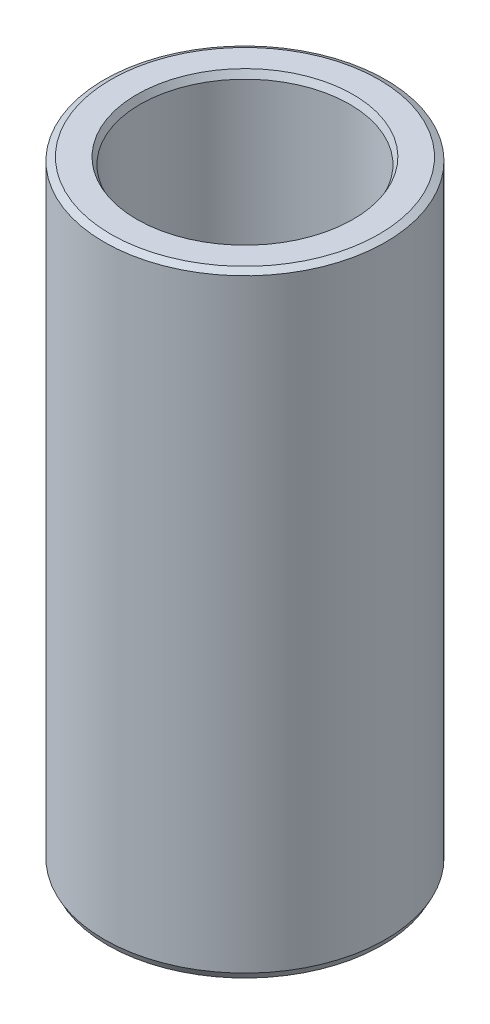
SolidWorks part; units mm, degrees
ref_plane "Front Plane" through (0, 0, 0) normal (0, 0, 1) x (1, 0, 0)
ref_plane "Top Plane" through (0, 0, 0) normal (0, 1, 0) x (1, 0, 0)
ref_plane "Right Plane" through (0, 0, 0) normal (1, 0, 0) x (0, 0, -1)
sketch "Sketch1" plane through (0, 0, 0) normal (0, 1, 0) x (1, 0, 0)
  circle A0 centre (0, 0) radius 60
  dimension "SLEEVE_OD" = 120
extrude "Boss-Extrude1" add sketch "Sketch1" along normal blind 261.7814
sketch "Sketch2" plane through (0, 0, 0) normal (0, 1, 0) x (1, 0, 0)
  circle A0 centre (0, 0) radius 44.6337
  dimension "BORE_D" = 89.2675
extrude "Cut-Extrude1" cut sketch "Sketch2" along normal through all
chamfer "Chamfer1" distance 1.4754 angle 62.681 4 edges at (0, 261.7814, 44.6337) (0, 0, 44.6337) (0, 0, 60) (0, 261.7814, 60) first distance on face at (0, 261.7814, 44.6337) first distance on face at (0, 0, 44.6337) first distance on face at (0, 261.7814, 60)
